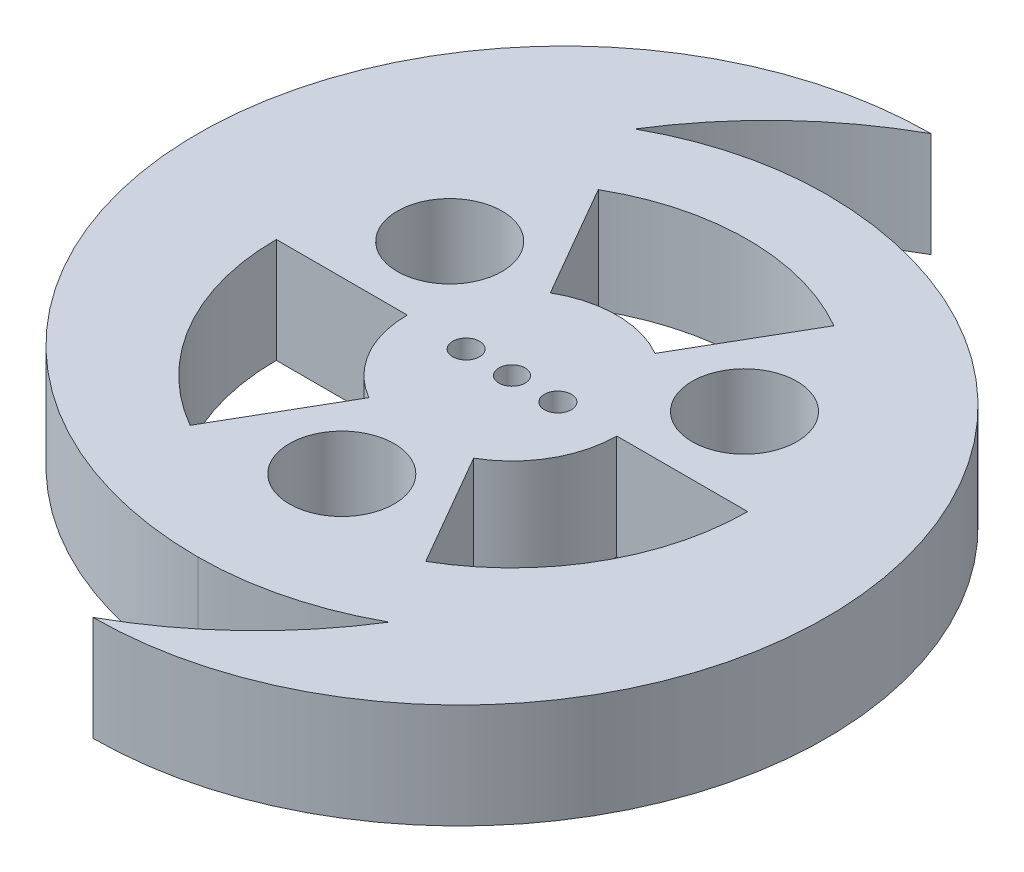
SolidWorks part; units mm, degrees
material "6061 Alloy"
ref_plane "Front Plane" through (0, 0, 0) normal (0, 0, 1) x (1, 0, 0)
ref_plane "Top Plane" through (0, 0, 0) normal (0, 1, 0) x (1, 0, 0)
ref_plane "Right Plane" through (0, 0, 0) normal (1, 0, 0) x (0, 0, -1)
sketch "Sketch1" plane through (0, 0, 0) normal (0, 1, 0) x (1, 0, 0)
  line L3 (-50.8, 50.8) -> (50.8, 50.8) construction
  line L4 (-50.8, 50.8) -> (-50.8, -50.8) construction
  line L5 (-50.8, -50.8) -> (50.8, -50.8) construction
  line L6 (50.8, 50.8) -> (50.8, -50.8) construction
  line L7 (-50.8, 50.8) -> (50.8, -50.8) construction
  line L8 (-50.8, -50.8) -> (50.8, 50.8) construction
  circle A0 centre (0, 0) radius 38.1
  arc A1 (0, 50.8) -> (0, -38.1) centre (0, 6.35) ccw
  arc A2 (0, -50.8) -> (0, 38.1) centre (0, -6.35) ccw
  arc A3 (0, 50.8) -> (0, -38.1) centre (24.5934, 6.35) ccw
  arc A4 (0, -50.8) -> (0, 38.1) centre (-24.5934, -6.35) ccw
  circle A5 centre (0, 0) radius 1.595
  point P9 (0, 0)
  point P20 (0, -50.8)
  point P23 (0, 50.8)
  dimension "D4" = 50.8
  dimension "D5" = 50.8
  dimension "D6" = 3.19
  dimension "D1" = 101.6
  dimension "D2" = 101.6
  dimension "D3" = 12.7
extrude "Boss-Extrude1" add sketch "Sketch1" along normal blind 12.7 contours A3 A1 A0 | A3 A0 | A0 A4 A3 | A4 A0 | A4 A2 A0 region at (26.4248, 0, -6.8228) region at (27.6436, 0, -27.6436) region at (23.698, 0, -6.1188) region at (-26.4248, 0, 6.8228) region at (-37.8525, 0, 9.7735)
sketch "Sketch2" plane through (0, 12.7, 0) normal (0, 1, 0) x (1, 0, 0)
  line L0 (-28.575, 0) -> (-12.7, 0)
  line L9 (-14.2875, -24.7467) -> (-6.35, -10.9985)
  line L10 (12.7, 0) -> (28.575, 0)
  line L15 (6.35, -10.9985) -> (14.2875, -24.7467)
  line L16 (-6.35, 10.9985) -> (-14.2875, 24.7467)
  line L17 (6.35, 10.9985) -> (14.2875, 24.7467)
  line L18 (-5.5626, 0) -> (5.5626, 0) construction
  arc A0 (-28.575, 0) -> (-14.2875, -24.7467) centre (0, 0) ccw
  arc A1 (-12.7, 0) -> (-6.35, -10.9985) centre (0, 0) ccw
  circle A3 centre (0, 0) radius 20.6375 construction
  arc A4 (14.2875, 24.7467) -> (-14.2875, 24.7467) centre (0, 0) ccw
  arc A5 (6.35, 10.9985) -> (-6.35, 10.9985) centre (0, 0) ccw
  arc A6 (6.35, -10.9985) -> (12.7, 0) centre (0, 0) ccw
  arc A7 (14.2875, -24.7467) -> (28.575, 0) centre (0, 0) ccw
  circle A8 centre (0, -20.6375) radius 6.35
  circle A9 centre (-17.8726, 10.3187) radius 6.35
  circle A10 centre (17.8726, 10.3188) radius 6.35
  point P19 (20.6375, 0)
  point P24 (0, 0)
  dimension "D1" = 25.4
  dimension "D2" = 57.15
  dimension "D6" = 12.7
  dimension "D3" = 60
  dimension "D4" = 60
  dimension "D5" = 60
  dimension "D8" = 11.1252
  dimension "D9" = 5.5626
  dimension "D7" = 3
extrude "Cut-Extrude1" cut sketch "Sketch2" against normal through all contours A5 L17 A4 L16 | A1 L0 A0 L9 | L15 A7 L10 A6 | A10 | A8 | A9 | A9 region at (-17.9086, 12.7, 10.3396) region at (17.9086, 12.7, 10.3396) region at (0, 12.7, -20.6791) region at (0, 12.7, 20.6375) region at (-17.8726, 12.7, -10.3187) region at (17.8726, 12.7, -10.3188)
hole_wizard "#4 Clearance Hole1" positions "Sketch3" profile "Sketch4" hole size "#4" standard "ANSI Inch" end condition through all
sketch "Sketch3" plane through (0, 12.7, 0) normal (0, 1, 0) x (1, 0, 0)
  point P0 (-5.5626, 0)
  point P3 (5.5626, 0)
sketch "Sketch4" plane through (-5.5626, 12.7, 0) normal (1, 0, 0) x (0, 0, 1)
  line L0 (0, 0) -> (0, 12.7)
  line L1 (0, 12.7) -> (1.6319, 12.7)
  line L2 (1.6319, 12.7) -> (1.6319, 0)
  line L5 (1.6319, 0) -> (0, 0)
  line L11 (0, -6.35) -> (0, 107.95) construction
  dimension "Thru Hole Dia." = 3.2639
  dimension "Thru Hole Depth" = 12.7
